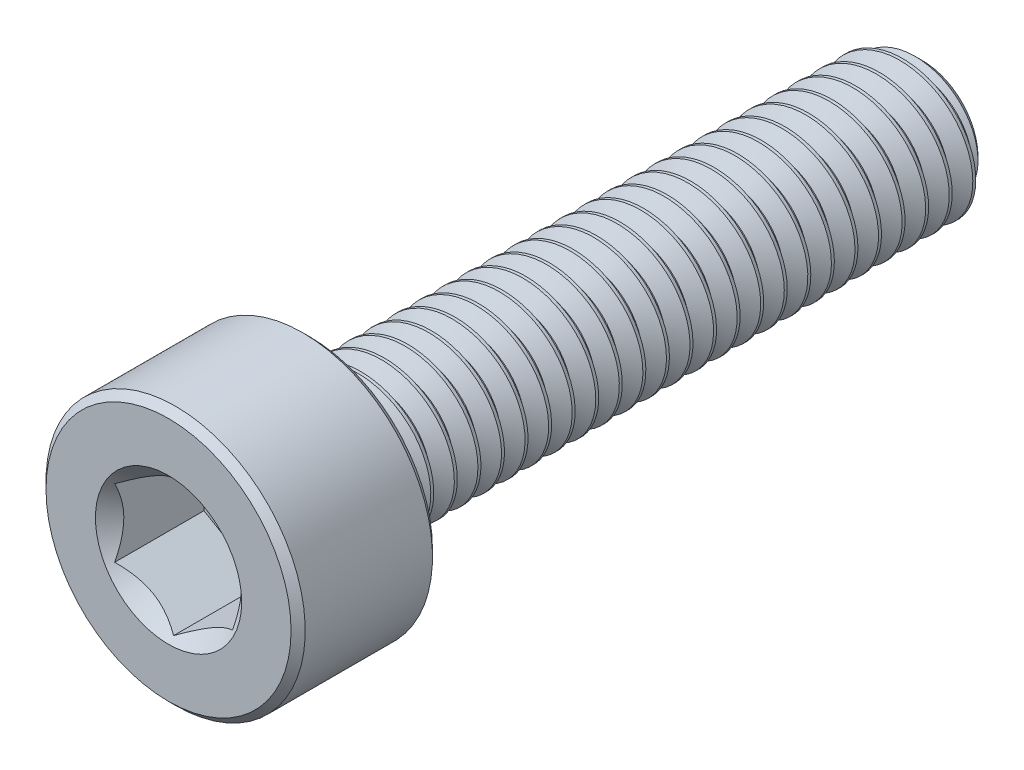
SolidWorks part; units mm, degrees
ref_plane "Front Plane" through (0, 0, 0) normal (0, 0, 1) x (1, 0, 0)
ref_plane "Top Plane" through (0, 0, 0) normal (0, 1, 0) x (1, 0, 0)
ref_plane "Right Plane" through (0, 0, 0) normal (1, 0, 0) x (0, 0, -1)
sketch "Sketch1" plane through (0, 0, 0) normal (1, 0, 0) x (0, 0, -1)
  line L0 (-8, 0) -> (8, 0) construction
  line L1 (8, 0) -> (8, 1.1752) construction
  line L2 (8, 1.1752) -> (7.6752, 1.5) construction
  line L3 (7.6752, 1.5) -> (7.625, 1.5) construction
  line L4 (7.625, 1.5) -> (-5, 1.5) construction
  line L5 (-5, 1.5) -> (-5, 2.75) construction
  line L6 (-5, 2.75) -> (-8, 2.75) construction
  line L7 (-8, 2.75) -> (-8, 0) construction
  line L8 (8, 1.1752) -> (8, 1.5) construction
  line L9 (7.9688, 1.5541) -> (8.2188, 1.1211) construction
  line L10 (8.2188, 1.1211) -> (8.4688, 1.5541) construction
  line L11 (8.4688, 1.5541) -> (7.9688, 1.5541) construction
  line L12 (8.2188, 1.5541) -> (8.2188, 1.5) construction
  line L13 (8.2188, 1.1211) -> (8.2188, 1.1752) construction
  line L14 (8.1875, 1.1752) -> (8.25, 1.1752) construction
  line L15 (8, 1.5) -> (8.4375, 1.5) construction
  line L16 (7.9844, 1.5271) -> (8.4531, 1.5271) construction
  line L17 (8, 0) -> (8, -1.5) construction
  line L18 (-5.15, 2.75) -> (-5, 2.6) construction
  line L19 (-7.85, 2.75) -> (-8, 2.6) construction
  line L20 (-5, 1.5) -> (-5, 0) construction
  line L21 (-5, 0.75) -> (-0.6667, 0.75) construction
  line L22 (-0.6667, 0.75) -> (3.6667, 0.75) construction
  line L23 (3.6667, 0.75) -> (8, 0.75) construction
  line L24 (-0.6667, 0.75) -> (-0.6667, 1.5) construction
  line L25 (-0.6667, 1.5) -> (-0.6667, 2.75) construction
  line L26 (3.6667, 0.75) -> (3.6667, 2.75) construction
  point P0 (-8, 1.25)
  point P3 (6.75, 1.5)
  point P4 (0, 0)
  point P18 (3.6667, 1.5)
  point P22 (8.2188, 1.1752)
  point P24 (7.625, 1.5)
  point P25 (8.2188, 1.5)
  point P28 (8.2188, 1.5271)
  point P29 (6.75, -1.5)
  point P30 (-0.6667, 1.5)
  point P31 (-6.5, 2.75)
  point P37 (-5.525, 2.75)
  point P38 (-7.775, 2.75)
  point P45 (-0.6667, 0.75)
  point P46 (3.6667, 0.75)
  dimension "D2" = 0.0625
  dimension "D7" = 0.15
  dimension "D8" = 0.15
  dimension "D9" = 0.15
  dimension "D10" = 0.075
  dimension "D11" = 0.375
  dimension "Drive Size" = 2.5
  dimension "Head Diameter" = 5.5
  dimension "Head Height" = 3
  dimension "Thread Pitch" = 0.5
  dimension "Thread Dia" = 3
  dimension "Length" = 13
  dimension "D12" = 0.375
  dimension "D4" = 1.25
  dimension "D3" = 45
sketch "Sketch2" plane through (0, 0, 0) normal (1, 0, 0) x (0, 0, -1)
  line L0 (-8, 0) -> (-8, 2.6)
  line L1 (-7.85, 2.75) -> (-5.15, 2.75)
  line L2 (-5, 2.6) -> (-5, 1.65)
  line L4 (7.6752, 1.5) -> (8, 1.1752)
  line L5 (8, 1.1752) -> (8, 0)
  line L6 (-5, 2.75) -> (-8, 2.75) construction
  line L7 (8, 0) -> (-8, 0)
  line L8 (-7.85, 2.75) -> (-8, 2.6) construction
  line L10 (-7.85, 2.75) -> (-8, 2.6)
  line L14 (-5.15, 2.75) -> (-5, 2.6) construction
  line L16 (-5.15, 2.75) -> (-5, 2.6)
  line L17 (-5, 1.5) -> (-5, 2.75) construction
  line L19 (-4.85, 1.5) -> (7.6752, 1.5)
  line L20 (7.625, 1.5) -> (-5, 1.5) construction
  arc A1 (-5, 1.65) -> (-4.85, 1.5) centre (-4.85, 1.65) ccw
  dimension "D3" = 0.15
revolve "Revolve1" add sketch "Sketch2" angle 360 about L7
sketch "Sketch3" plane through (0, 0, 8) normal (0, 0, 1) x (1, 0, 0)
  line L1 (1.25, -0.7217) -> (1.25, 0.7217)
  line L2 (1.25, 0.7217) -> (0, 1.4434)
  line L3 (0, 1.4434) -> (-1.25, 0.7217)
  line L4 (-1.25, 0.7217) -> (-1.25, -0.7217)
  line L5 (-1.25, -0.7217) -> (0, -1.4434)
  line L6 (0, -1.4434) -> (1.25, -0.7217)
  circle A0 centre (0, 0) radius 1.25 construction
  circle A1 centre (0, 0) radius 2.75 construction
  circle A2 centre (0, 0) radius 2.75 construction
  circle A3 centre (0, 0) radius 1.4434 construction
  point P13 (0, 0)
  dimension "D1" = 2.8868
extrude "Cut-Extrude1" cut sketch "Sketch3" against normal offset from surface (2 mm away) 1 up to face at (0, 2.6, 5)
sketch "Sketch4" plane through (0, 0, 8) normal (0, 0, 1) x (1, 0, 0)
  circle A0 centre (0, 0) radius 1.5516
  dimension "D1" = 3.1033
extrude "Cut-Extrude2" cut sketch "Sketch4" against normal up to vertex (1.5 mm away) draft 45 up to point (0, 2.75, 6.5)
sketch "Sketch11" plane through (0, 0, 0) normal (1, 0, 0) x (0, 0, -1)
  line L0 (-8, 0) -> (8, 0) construction
  line L1 (-8, 0) -> (8, 0) construction
  line L2 (-2.5625, 0) -> (-2.5625, 1.5) construction
  line L3 (7.625, 1.5) -> (-5, 1.5) construction
  line L4 (5.5625, 0) -> (5.5625, 1.5) construction
  line L6 (8, 1.1752) -> (8, 1.5) construction
  point P2 (-2.5625, 0)
  point P3 (5.5625, 0)
  dimension "D1" = 2.4375
  dimension "D2" = 2.4375
sketch "Sketch6" plane through (0, 0, -8) normal (0, 0, -1) x (-1, 0, 0)
  circle A0 centre (0, 0) radius 1.5
curve "Helix/Spiral1" pitch 0.5 height 13.5 turns 27
sketch "Sketch10" plane through (0, 0, 0) normal (1, 0, 0) x (0, 0, -1)
  line L0 (-4.85, -2.75) -> (-4.85, 2.75)
  line L5 (-8, 0) -> (8, 0) construction
  line L6 (-4.85, 1.5) -> (-4.85, -1.5) construction
  point P3 (-4.85, 0)
split "Split1" trim tools "Sketch10" bodies to split 106 resulting bodies 114 115
sketch "Sketch7" plane through (0, 0, 0) normal (1, 0, 0) x (0, 0, -1)
  line L0 (7.9844, 1.5271) -> (8.4531, 1.5271)
  line L1 (8.4531, 1.5271) -> (8.25, 1.1752)
  line L2 (8.25, 1.1752) -> (8.1875, 1.1752)
  line L3 (8.1875, 1.1752) -> (7.9844, 1.5271)
sweep "Cut-Sweep1" cut profiles "Sketch7" path "Helix/Spiral1" align with end faces yes
sketch "Sketch8" plane through (0, 0, 0) normal (1, 0, 0) x (0, 0, -1)
  line L0 (-5, 0) -> (-5, 1.5)
  line L1 (-4.85, -1.5) -> (-4.85, 1.5) construction
  line L2 (-5, 1.5) -> (-4.85, 1.5)
  line L4 (-4.85, 1.5) -> (-3.984, 0)
  line L5 (-3.984, 0) -> (-5, 0)
  line L6 (7.625, 1.5) -> (-5, 1.5) construction
  line L7 (-8, 0) -> (8, 0) construction
  dimension "D1" = 60
revolve "Revolve2" add sketch "Sketch8" angle 360 about L5
equation "\"D2@Sketch1\" = \"Thread Pitch@Sketch1\" / 8"
equation "\"D4@Helix/Spiral1\" = \"Thread Pitch@Sketch1\""
equation "\"D7@Sketch1\" = \"Head Height@Sketch1\" * .05"
equation "\"D8@Sketch1\"=\"D7@Sketch1\""
equation "\"D9@Sketch1\"=\"D7@Sketch1\""
equation "\"D10@Sketch1\"=\"D7@Sketch1\"/2"
equation "\"D11@Sketch1\"=\"D10@Sketch1\"*5"
equation "\"D4@Sketch1\"=\"Thread Pitch@Sketch1\"*2.5"
equation "\"D12@Sketch1\"=\"Thread Pitch@Sketch1\"*.75"
equation "\"D3@Helix/Spiral1\"=\"Length@Sketch1\"+\"Thread Pitch@Sketch1\""
equation "\"D3@Sketch2\"=\"Thread Dia@Sketch1\"*0.05"
equation "\"D1@Sketch11\"=\"Length@Sketch1\"*0.1875"
equation "\"D2@Sketch11\"=\"D1@Sketch11\""
equation "\"D1@Sketch4\"=\"D1@Sketch3\"*1.075"
